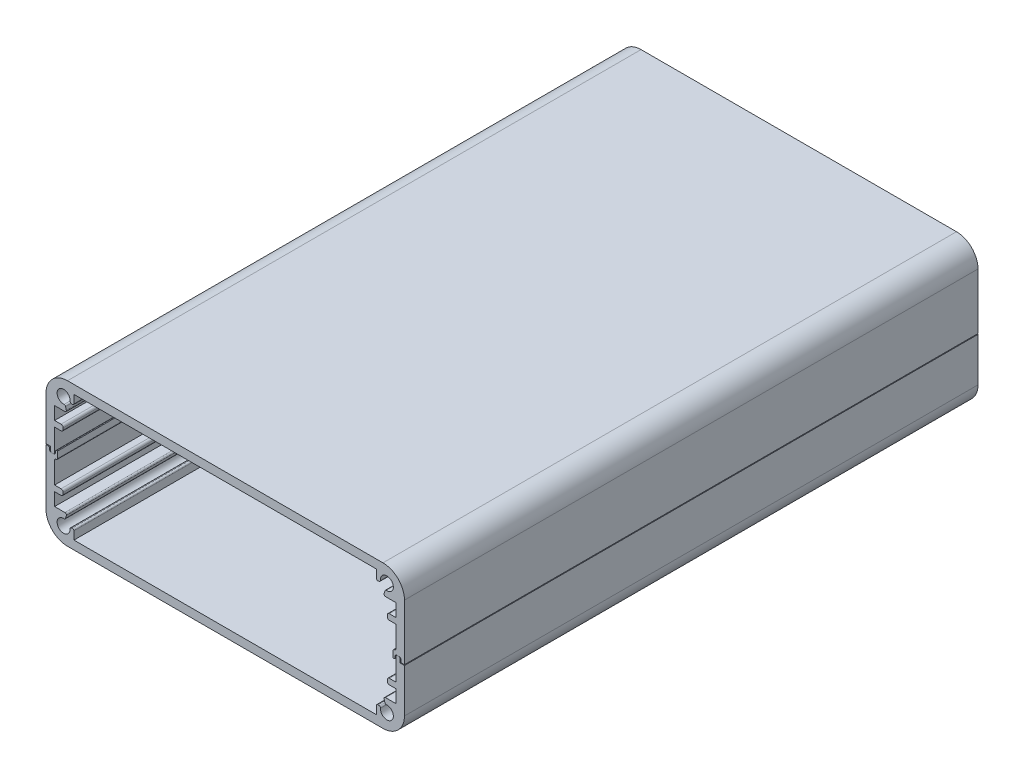
SolidWorks part; units mm, degrees
ref_plane "前视基准面" through (0, 0, 0) normal (0, 0, 1) x (1, 0, 0)
ref_plane "上视基准面" through (0, 0, 0) normal (0, 1, 0) x (1, 0, 0)
ref_plane "右视基准面" through (0, 0, 0) normal (1, 0, 0) x (0, 0, -1)
sketch "草图5" plane through (0, 0, 0) normal (0, 0, 1) x (1, 0, 0)
  line L0 (47.55, 0.8) -> (47.55, 6.9)
  line L1 (46.35, 1.7) -> (46.35, 3.5)
  line L2 (46.35, 4.3) -> (46.35, 7.4)
  line L3 (46.95, 6.9) -> (46.95, 7.4)
  line L4 (-2.45, 0.8) -> (-2.45, 8.6)
  line L5 (-1.95, 8.2) -> (-1.95, 8.4)
  line L6 (-0.85, 7.7) -> (-0.85, 8.6)
  line L7 (-1.15, 8.2) -> (-1.15, 8.4)
  line L8 (-1.25, 1.7) -> (-1.25, 3.5)
  line L9 (-1.25, 4.3) -> (-1.25, 7.3)
  line L10 (44.55, -2.2) -> (0.55, -2.2)
  line L11 (44.0552, 0.28) -> (43.9018, 0.3211)
  line L12 (46.75, 7.6) -> (46.55, 7.6)
  line L13 (47.55, 6.9) -> (46.95, 6.9)
  line L14 (46.35, 1.7) -> (44.9051, 1.7)
  line L15 (46.35, 3.5) -> (45.45, 3.5)
  line L16 (46.35, 4.3) -> (45.45, 4.3)
  line L17 (43.65, -1) -> (1.45, -1)
  line L18 (-0.85, 8.6) -> (-0.95, 8.6)
  line L19 (-2.15, 8.6) -> (-2.45, 8.6)
  line L20 (-1.35, 8) -> (-1.75, 8)
  line L21 (44.7119, 1.4482) -> (44.82, 1.0448)
  line L22 (45.15, 4) -> (45.15, 3.8)
  line L23 (43.65, -1) -> (43.65, 0.1279)
  line L24 (-1.25, 1.7) -> (0.1949, 1.7)
  line L25 (1.45, -1) -> (1.45, 0.1279)
  line L26 (-1.25, 3.5) -> (-0.35, 3.5)
  line L27 (-1.25, 4.3) -> (-0.35, 4.3)
  line L28 (-0.05, 4) -> (-0.05, 3.8)
  line L29 (1.0448, 0.28) -> (1.1982, 0.3211)
  line L30 (0.3881, 1.4482) -> (0.28, 1.0448)
  line L31 (-2.45, 14.8) -> (-2.45, 8.7)
  line L32 (-1.25, 13.9) -> (-1.25, 12.1)
  line L33 (-1.25, 11.3) -> (-1.25, 8.2)
  line L34 (-1.85, 8.7) -> (-1.85, 8.2)
  line L35 (47.55, 14.8) -> (47.55, 7)
  line L36 (47.05, 7.4) -> (47.05, 7.2)
  line L37 (45.95, 7.9) -> (45.95, 7)
  line L38 (46.25, 7.4) -> (46.25, 7.2)
  line L39 (46.35, 13.9) -> (46.35, 12.1)
  line L40 (46.35, 11.3) -> (46.35, 8.3)
  line L41 (0.55, 17.8) -> (44.55, 17.8)
  line L42 (1.0448, 15.32) -> (1.1982, 15.2789)
  line L43 (-1.65, 8) -> (-1.45, 8)
  line L44 (-2.45, 8.7) -> (-1.85, 8.7)
  line L45 (-1.25, 13.9) -> (0.1949, 13.9)
  line L46 (-1.25, 12.1) -> (-0.35, 12.1)
  line L47 (-1.25, 11.3) -> (-0.35, 11.3)
  line L48 (1.45, 16.6) -> (43.65, 16.6)
  line L49 (45.95, 7) -> (46.05, 7)
  line L50 (47.25, 7) -> (47.55, 7)
  line L51 (46.45, 7.6) -> (46.85, 7.6)
  line L52 (0.3881, 14.1518) -> (0.28, 14.5552)
  line L53 (-0.05, 11.6) -> (-0.05, 11.8)
  line L54 (1.45, 16.6) -> (1.45, 15.4721)
  line L55 (46.35, 13.9) -> (44.9051, 13.9)
  line L56 (43.65, 16.6) -> (43.65, 15.4721)
  line L57 (46.35, 12.1) -> (45.45, 12.1)
  line L58 (46.35, 11.3) -> (45.45, 11.3)
  line L59 (45.15, 11.6) -> (45.15, 11.8)
  line L60 (44.0552, 15.32) -> (43.9018, 15.2789)
  line L61 (44.7119, 14.1518) -> (44.82, 14.5552)
  arc A0 (46.55, 7.6) -> (46.35, 7.4) centre (46.55, 7.4) ccw
  arc A1 (46.95, 7.4) -> (46.75, 7.6) centre (46.75, 7.4) ccw
  arc A2 (-1.95, 8.4) -> (-2.15, 8.6) centre (-2.15, 8.4) ccw
  arc A3 (-1.05, 7.5) -> (-1.25, 7.3) centre (-1.05, 7.3) ccw
  arc A4 (-2.45, 0.8) -> (0.55, -2.2) centre (0.55, 0.8) ccw
  arc A5 (45.45, 4.3) -> (45.15, 4) centre (45.45, 4) ccw
  arc A6 (44.55, -2.2) -> (47.55, 0.8) centre (44.55, 0.8) ccw
  arc A7 (-0.95, 8.6) -> (-1.15, 8.4) centre (-0.95, 8.4) ccw
  arc A8 (-1.35, 8) -> (-1.15, 8.2) centre (-1.35, 8.2) ccw
  arc A9 (-1.95, 8.2) -> (-1.75, 8) centre (-1.75, 8.2) ccw
  arc A10 (-1.05, 7.5) -> (-0.85, 7.7) centre (-1.05, 7.7) ccw
  arc A11 (44.9051, 1.7) -> (44.7119, 1.4482) centre (44.9051, 1.5) ccw
  arc A12 (45.15, 3.8) -> (45.45, 3.5) centre (45.45, 3.8) ccw
  arc A13 (43.9018, 0.3211) -> (43.65, 0.1279) centre (43.85, 0.1279) ccw
  arc A14 (0.3881, 1.4482) -> (0.1949, 1.7) centre (0.1949, 1.5) ccw
  arc A15 (1.45, 0.1279) -> (1.1982, 0.3211) centre (1.25, 0.1279) ccw
  arc A16 (-0.05, 4) -> (-0.35, 4.3) centre (-0.35, 4) ccw
  arc A17 (-0.35, 3.5) -> (-0.05, 3.8) centre (-0.35, 3.8) ccw
  arc A18 (44.2028, 0.071) -> (45.029, 0.8972) centre (45.1, 0) ccw
  arc A19 (44.2028, 0.071) -> (44.0552, 0.28) centre (44.0034, 0.0868) ccw
  arc A20 (44.82, 1.0448) -> (45.029, 0.8972) centre (45.0132, 1.0966) ccw
  arc A21 (0.071, 0.8972) -> (0.8972, 0.071) centre (0, 0) ccw
  arc A22 (1.0448, 0.28) -> (0.8972, 0.071) centre (1.0966, 0.0868) ccw
  arc A23 (0.071, 0.8972) -> (0.28, 1.0448) centre (0.0868, 1.0966) ccw
  arc A24 (-1.45, 8) -> (-1.25, 8.2) centre (-1.45, 8.2) ccw
  arc A25 (-1.85, 8.2) -> (-1.65, 8) centre (-1.65, 8.2) ccw
  arc A26 (47.05, 7.2) -> (47.25, 7) centre (47.25, 7.2) ccw
  arc A27 (46.15, 8.1) -> (46.35, 8.3) centre (46.15, 8.3) ccw
  arc A28 (47.55, 14.8) -> (44.55, 17.8) centre (44.55, 14.8) ccw
  arc A29 (-0.35, 11.3) -> (-0.05, 11.6) centre (-0.35, 11.6) ccw
  arc A30 (0.55, 17.8) -> (-2.45, 14.8) centre (0.55, 14.8) ccw
  arc A31 (46.05, 7) -> (46.25, 7.2) centre (46.05, 7.2) ccw
  arc A32 (46.45, 7.6) -> (46.25, 7.4) centre (46.45, 7.4) ccw
  arc A33 (47.05, 7.4) -> (46.85, 7.6) centre (46.85, 7.4) ccw
  arc A34 (46.15, 8.1) -> (45.95, 7.9) centre (46.15, 7.9) ccw
  arc A35 (0.1949, 13.9) -> (0.3881, 14.1518) centre (0.1949, 14.1) ccw
  arc A36 (-0.05, 11.8) -> (-0.35, 12.1) centre (-0.35, 11.8) ccw
  arc A37 (1.1982, 15.2789) -> (1.45, 15.4721) centre (1.25, 15.4721) ccw
  arc A38 (44.7119, 14.1518) -> (44.9051, 13.9) centre (44.9051, 14.1) ccw
  arc A39 (43.65, 15.4721) -> (43.9018, 15.2789) centre (43.85, 15.4721) ccw
  arc A40 (45.15, 11.6) -> (45.45, 11.3) centre (45.45, 11.6) ccw
  arc A41 (45.45, 12.1) -> (45.15, 11.8) centre (45.45, 11.8) ccw
  arc A42 (0.8972, 15.529) -> (0.071, 14.7028) centre (0, 15.6) ccw
  arc A43 (0.8972, 15.529) -> (1.0448, 15.32) centre (1.0966, 15.5132) ccw
  arc A44 (0.28, 14.5552) -> (0.071, 14.7028) centre (0.0868, 14.5034) ccw
  arc A45 (45.029, 14.7028) -> (44.2028, 15.529) centre (45.1, 15.6) ccw
  arc A46 (44.0552, 15.32) -> (44.2028, 15.529) centre (44.0034, 15.5132) ccw
  arc A47 (45.029, 14.7028) -> (44.82, 14.5552) centre (45.0132, 14.5034) ccw
extrude "凸台-拉伸1" add sketch "草图5" along normal blind 80 contours L41 A28 L35 L50 A26 L36 A33 L51 A32 L38 A31 L49 L37 A34 A27 L40 L58 A40 L59 A41 L57 L39 L55 A38 L61 A47 A45 A46 L60 A39 L56 L48 L54 A37 L42 A43 A42 A44 L52 A35 L45 L32 L46 A36 L53 A29 L47 L33 A24 L43 A25 L34 L44 L31 A30
extrude "凸台-拉伸2" add sketch "草图5<3>" along normal blind 80 separate body contours L10 A4 L4 L19 A2 L5 A9 L20 A8 L7 A7 L18 L6 A10 A3 L9 L27 A16 L28 A17 L26 L8 L24 A14 L30 A23 A21 A22 L29 A15 L25 L17 L23 A13 L11 A19 A18 A20 L21 A11 L14 L1 L15 A12 L22 A5 L16 L2 A0 L12 A1 L3 L13 L0 A6
sketch "草图5<3>" plane through (0, 0, 0) normal (0, 0, 1) x (1, 0, 0) same geometry as "草图5"
